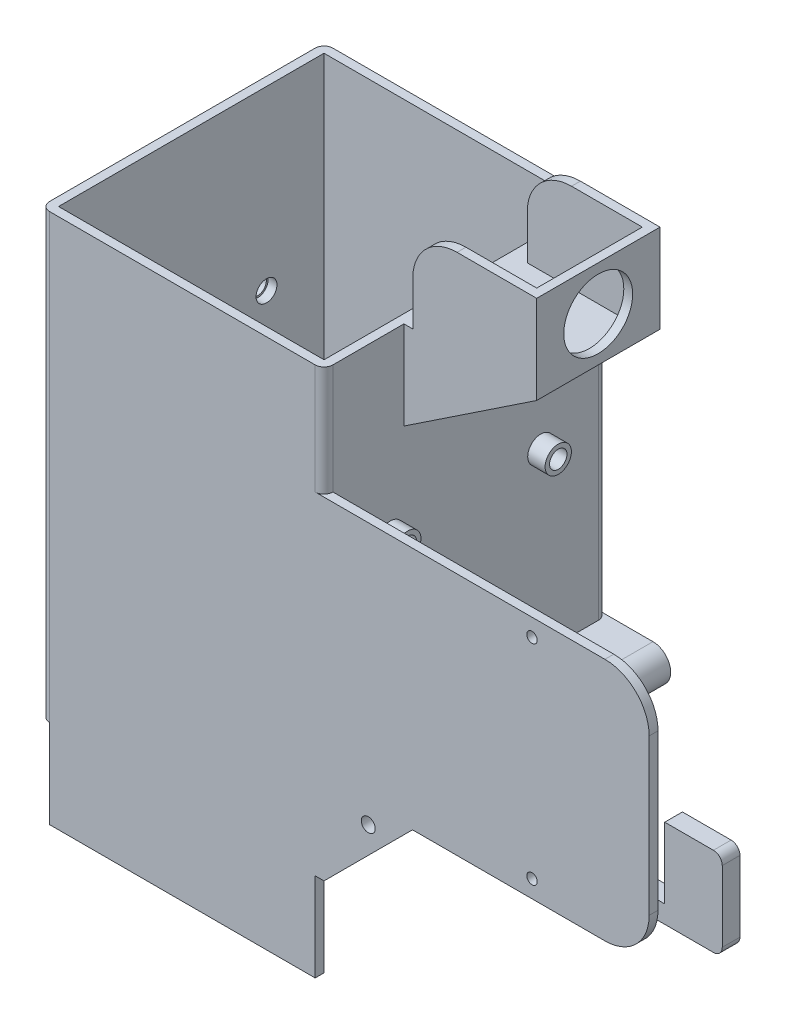
SolidWorks part; units mm, degrees
ref_plane "Front Plane" through (0, 0, 0) normal (0, 0, 1) x (1, 0, 0)
ref_plane "Top Plane" through (0, 0, 0) normal (0, 1, 0) x (1, 0, 0)
ref_plane "Right Plane" through (0, 0, 0) normal (1, 0, 0) x (0, 0, -1)
sketch "Sketch1" plane through (0, 0, 0) normal (0, 1, 0) x (1, 0, 0)
  line L1 (0, 0) -> (81.28, 0)
  line L2 (0, 0) -> (0, 81.28)
  line L3 (0, 81.28) -> (81.28, 81.28)
  line L4 (81.28, 0) -> (81.28, 81.28)
  line L5 (2.54, 2.54) -> (78.74, 2.54)
  line L6 (2.54, 2.54) -> (2.54, 78.74)
  line L7 (2.54, 78.74) -> (78.74, 78.74)
  line L8 (78.74, 2.54) -> (78.74, 78.74)
  dimension "D1" = 2.54
  dimension "D2" = 2.54
  dimension "D3" = 2.54
  dimension "D4" = 2.54
  dimension "D5" = 76.2
  dimension "D6" = 76.2
extrude "Boss-Extrude1" add sketch "Sketch1" along normal blind 177.8
sketch "Sketch2" plane through (0, 0, 0) normal (1, 0, 0) x (0, 0, -1)
  line L0 (109.0297, 38.1) -> (-23.7268, 38.1) construction
  line L1 (81.28, 0) -> (0, 0) construction
  line L2 (40.64, -8.2418) -> (40.64, 63.9342) construction
  line L3 (81.28, 177.8) -> (81.28, 0) construction
  line L5 (66.04, 0) -> (63.5, 0)
  line L6 (66.04, 0) -> (66.04, 38.1)
  line L7 (66.04, 38.1) -> (63.5, 38.1)
  line L8 (63.5, 0) -> (63.5, 38.1)
  dimension "D1" = 38.1
  dimension "D2" = 40.64
  dimension "D3" = 2.54
  dimension "D4" = 15.24
extrude "Boss-Extrude2" add sketch "Sketch2" against normal blind 25.4
sketch "Sketch3" plane through (0, 0, 0) normal (0, 0, 1) x (1, 0, 0)
  line L1 (81.28, 0) -> (78.74, 0)
  line L2 (81.28, 0) -> (81.28, 25.4)
  line L3 (81.28, 25.4) -> (78.74, 25.4)
  line L4 (78.74, 0) -> (78.74, 25.4)
  dimension "D1" = 2.54
  dimension "D2" = 25.4
extrude "Cut-Extrude1" cut sketch "Sketch3" against normal through all
sketch "Sketch7" plane through (0, 0, 0) normal (0, 0, 1) x (1, 0, 0)
  line L0 (81.28, 25.4) -> (106.68, 50.8)
  line L1 (106.68, 50.8) -> (81.28, 50.8)
  line L2 (81.28, 177.8) -> (81.28, 25.4) construction
  line L3 (81.28, 50.8) -> (81.28, 25.4)
  dimension "D1" = 45
  dimension "D2" = 25.4
extrude "Boss-Extrude3" add sketch "Sketch7" against normal blind 12.7
sketch "Sketch10" plane through (0, 0, -81.28) normal (0, 0, -1) x (-1, 0, 0)
  line L0 (-81.28, 25.4) -> (-81.28, 50.8)
  line L1 (-81.28, 177.8) -> (-81.28, 25.4) construction
  line L2 (-81.28, 50.8) -> (-106.68, 50.8)
  line L3 (-106.68, 50.8) -> (-81.28, 25.4)
  dimension "D1" = 45
  dimension "D2" = 25.4
extrude "Boss-Extrude4" add sketch "Sketch10" against normal blind 12.7
sketch "Sketch14" plane through (81.28, 0, 0) normal (1, 0, 0) x (0, 0, -1)
  line L0 (38.1, 50.8) -> (38.1, 25.4)
  line L1 (68.58, 25.4) -> (12.7, 25.4) construction
  line L2 (38.1, 25.4) -> (43.18, 25.4)
  line L3 (43.18, 25.4) -> (43.18, 50.8)
  line L4 (43.18, 50.8) -> (38.1, 50.8)
  line L5 (68.58, 50.8) -> (68.58, 25.4) construction
  dimension "D1" = 5.08
  dimension "D2" = 25.4
  dimension "D3" = 25.4
extrude "Boss-Extrude6" add sketch "Sketch14" along normal blind 76.2
sketch "Sketch16" plane through (0, 0, -38.1) normal (0, 0, 1) x (1, 0, 0)
  line L0 (157.48, 50.8) -> (81.28, 50.8) construction
  line L1 (140.97, 50.8) -> (117.84, 50.8)
  line L2 (140.97, 50.8) -> (140.97, 30.48)
  line L3 (140.97, 30.48) -> (117.84, 30.48)
  line L4 (117.84, 50.8) -> (117.84, 30.48)
  line L5 (157.48, 50.8) -> (157.48, 25.4) construction
  line L6 (157.48, 25.4) -> (81.28, 25.4) construction
  dimension "D1" = 16.51
  dimension "D2" = 23.13
  dimension "D3" = 5.08
extrude "Cut-Extrude2" cut sketch "Sketch16" against normal up to next
sketch "Sketch22" plane through (0, 0, 0) normal (0, 0, 1) x (1, 0, 0)
  line L0 (93.98, 45.72) -> (101.6, 45.72) construction
  line L1 (106.68, 50.8) -> (81.28, 50.8) construction
  line L2 (93.98, 50.8) -> (93.98, 45.72) construction
  line L4 (81.28, 25.4) -> (106.68, 50.8) construction
  circle A0 centre (93.98, 45.72) radius 2
  dimension "D3" = 4
  dimension "D1" = 5.08
  dimension "D2" = 12.7
extrude "Cut-Extrude6" cut sketch "Sketch22" against normal through all
sketch "Sketch28" plane through (81.28, 0, 0) normal (1, 0, 0) x (0, 0, -1)
  line L0 (40.64, 175.678) -> (40.64, 120.0937) construction
  line L1 (40.64, 184.0271) -> (40.64, -14.0592) construction
  line L2 (0, 177.8) -> (81.28, 177.8) construction
  line L3 (0, 177.8) -> (0, 50.8) construction
  line L5 (58.34, 177.8) -> (22.94, 177.8)
  line L6 (58.34, 177.8) -> (58.34, 127)
  line L7 (58.34, 127) -> (22.94, 127)
  line L8 (22.94, 177.8) -> (22.94, 127)
  line L9 (58.34, 177.8) -> (22.94, 127) construction
  line L10 (58.34, 127) -> (22.94, 177.8) construction
  point P8 (40.64, 109.22)
  dimension "D2" = 40.64
  dimension "D3" = 50.8
  dimension "D4" = 35.4
extrude "Boss-Extrude7" add sketch "Sketch28" along normal blind 38.1
sketch "Sketch30" plane through (0, 0, -22.94) normal (0, 0, 1) x (1, 0, 0)
  line L0 (81.28, 127) -> (119.38, 127)
  line L1 (119.38, 127) -> (119.38, 152.4)
  line L3 (119.38, 152.4) -> (81.28, 127)
  dimension "D1" = 25.4
  dimension "D2" = 33.69
extrude "Cut-Extrude8" cut sketch "Sketch30" against normal up to next
sketch "Sketch32" plane through (0, 177.8, 0) normal (0, 1, 0) x (1, 0, 0)
  line L0 (119.38, 58.34) -> (81.28, 58.34) construction
  line L1 (83.82, 55.8) -> (116.84, 55.8)
  line L2 (83.82, 55.8) -> (83.82, 25.48)
  line L3 (83.82, 25.48) -> (116.84, 25.48)
  line L4 (116.84, 55.8) -> (116.84, 25.48)
  line L5 (83.82, 55.8) -> (116.84, 25.48) construction
  line L6 (83.82, 25.48) -> (116.84, 55.8) construction
  line L7 (119.38, 58.34) -> (119.38, 22.94) construction
  line L8 (119.38, 22.94) -> (81.28, 22.94) construction
  line L9 (81.28, 58.34) -> (81.28, 81.28) construction
  point P0 (100.33, 40.64)
  dimension "D1" = 2.54
  dimension "D2" = 2.54
  dimension "D3" = 2.54
  dimension "D4" = 2.54
extrude "Cut-Extrude9" cut sketch "Sketch32" against normal blind 25.4
sketch "Sketch34" plane through (119.38, 0, 0) normal (1, 0, 0) x (0, 0, -1)
  line L0 (40.593, 147.7754) -> (40.593, 78.4323) construction
  line L1 (11.6001, 165.1) -> (93.4551, 165.1) construction
  line L2 (22.94, 177.8) -> (22.94, 152.4) construction
  line L3 (58.34, 177.8) -> (22.94, 177.8) construction
  circle A0 centre (40.593, 165.1) radius 9.89
  dimension "D3" = 19.78
  dimension "D1" = 17.653
  dimension "D2" = 12.7
extrude "Cut-Extrude13" cut sketch "Sketch34" against normal up to surface (40.64 mm away) up to face at (78.74, 101.6, -40.64)
sketch "Sketch37" plane through (0, 0, -63.5) normal (0, 0, 1) x (1, 0, 0)
  line L0 (-25.4, 38.1) -> (0, 38.1)
  line L1 (0, 38.1) -> (0, 52.7647)
  line L2 (0, 52.7647) -> (-25.4, 38.1)
  dimension "D1" = 30
extrude "Boss-Extrude9" add sketch "Sketch37" against normal up to surface (2.54 mm away) up to face at (-12.7, 19.05, -66.04)
sketch "Sketch38" plane through (0, 0, 0) normal (0, 0, 1) x (1, 0, 0)
  line L1 (0, 0) -> (2.54, 0)
  line L2 (0, 0) -> (0, 25.4)
  line L3 (0, 25.4) -> (2.54, 25.4)
  line L4 (2.54, 0) -> (2.54, 25.4)
  dimension "D1" = 25.4
  dimension "D2" = 2.54
extrude "Cut-Extrude15" cut sketch "Sketch38" against normal up to surface (63.5 mm away) up to face at (-12.7, 22.7162, -63.5)
sketch "Sketch40" plane through (81.28, 0, 0) normal (1, 0, 0) x (0, 0, -1)
  line L0 (-23.3344, 101.6) -> (103.8421, 101.6) construction
  line L1 (38.1, 25.4) -> (12.7, 25.4) construction
  line L2 (19.05, 177.8) -> (19.05, 25.4) construction
  line L3 (62.23, 177.8) -> (62.23, 25.4) construction
  line L6 (0, 177.8) -> (0, 50.8) construction
  line L7 (81.28, 177.8) -> (81.28, 50.8) construction
  line L8 (0, 177.8) -> (22.94, 177.8) construction
  line L9 (58.34, 177.8) -> (81.28, 177.8) construction
  line L10 (68.58, 25.4) -> (43.18, 25.4) construction
  circle A0 centre (19.05, 101.6) radius 3
  circle A1 centre (62.23, 101.6) radius 3
  dimension "D4" = 6
  dimension "D5" = 6
  dimension "D1" = 76.2
  dimension "D2" = 19.05
  dimension "D3" = 19.05
extrude "Cut-Extrude17" cut sketch "Sketch40" against normal up to surface (81.28 mm away) up to face at (0, 63.9912, -52.705)
sketch "Sketch41" plane through (81.28, 0, 0) normal (1, 0, 0) x (0, 0, -1)
  circle A0 centre (19.05, 101.6) radius 3.77
  circle A1 centre (19.05, 101.6) radius 2.5
  circle A2 centre (62.23, 101.6) radius 3.77
  circle A4 centre (62.23, 101.6) radius 2.5
  dimension "D1" = 1.27
  dimension "D2" = 1.27
extrude "Boss-Extrude10" add sketch "Sketch41" along normal blind 5
sketch "Sketch42" plane through (0, 0, 0) normal (-1, 0, 0) x (0, 0, 1)
  circle A0 centre (-62.23, 101.6) radius 2.5
  circle A1 centre (-62.23, 101.6) radius 3.77
  circle A2 centre (-19.05, 101.6) radius 2.5
  circle A3 centre (-19.05, 101.6) radius 3.77
  dimension "D1" = 1.27
  dimension "D2" = 1.27
extrude "Boss-Extrude11" add sketch "Sketch42" along normal blind 5
sketch "Sketch43" plane through (0, 177.8, 0) normal (0, 1, 0) x (1, 0, 0)
  line L1 (83.82, 58.34) -> (83.82, 22.94)
  line L3 (78.74, 2.54) -> (2.54, 2.54)
  line L4 (2.54, 2.54) -> (78.74, 2.54) construction
  line L5 (2.54, 2.54) -> (2.54, 78.74)
  line L6 (2.54, 78.74) -> (78.74, 78.74)
  line L11 (81.28, 81.28) -> (0, 81.28)
  line L12 (0, 81.28) -> (0, 0)
  line L13 (0, 0) -> (81.28, 0)
  line L19 (81.28, 81.28) -> (81.28, 58.34)
  line L21 (81.28, 58.34) -> (83.82, 58.34)
  line L22 (81.28, 0) -> (81.28, 22.94)
  line L23 (81.28, 22.94) -> (83.82, 22.94)
  line L24 (78.74, 78.74) -> (78.74, 2.54)
  line L25 (83.82, 55.8) -> (83.82, 25.48) construction
  line L26 (119.38, 22.94) -> (81.28, 22.94) construction
  line L27 (81.28, 81.28) -> (0, 81.28) construction
extrude "Cut-Extrude20" cut sketch "Sketch43" against normal blind 25.4
sketch "Sketch44" plane through (0, 0, 0) normal (0, 0, 1) x (1, 0, 0)
  line L0 (0, 152.4) -> (0, 25.4) construction
  line L1 (0, 50.8) -> (174.6, 50.8)
  line L2 (0, 50.8) -> (0, 120.8)
  line L3 (0, 120.8) -> (174.6, 120.8)
  line L4 (174.6, 50.8) -> (174.6, 120.8)
  line L5 (106.68, 50.8) -> (81.28, 50.8) construction
  line L6 (-25.4, 38.1) -> (-25.4, 0) construction
  line L7 (140.97, 50.8) -> (140.97, 120.8) construction
  line L8 (140.97, 30.48) -> (140.97, 50.8) construction
  circle A0 centre (140.97, 115.8) radius 1.5
  circle A1 centre (140.97, 55.8) radius 1.5
  dimension "D3" = 3
  dimension "D1" = 200
  dimension "D2" = 70
  dimension "D4" = 60
  dimension "D5" = 5
extrude "Boss-Extrude12" add sketch "Sketch44" against normal blind 2.54
fillet "Fillet1" radius 5.08 2 edges at (106.68, 50.8, -7.62) (106.68, 50.8, -74.93)
fillet "Fillet2" radius 12.7 2 edges at (174.6, 120.8, -1.27) (174.6, 50.8, -1.27)
fillet "Fillet3" radius 2.54 2 edges at (157.48, 50.8, -40.64) (157.48, 25.4, -40.64)
fillet "Fillet7" radius 12.7 1 edges at (-25.4, 38.1, -64.77)
fillet "Fillet9" radius 12.7 2 edges at (83.82, 177.8, -24.21) (83.82, 177.8, -57.07)
sketch "Sketch53" plane through (0, 0, 0) normal (0, -1, 0) x (-1, 0, 0)
  line L0 (-35.6591, 81.28) -> (-35.6591, 78.74)
  line L1 (-78.74, 81.28) -> (0, 81.28) construction
  line L2 (-78.74, 78.74) -> (-2.54, 78.74) construction
  line L3 (-35.6591, 78.74) -> (-45.72, 78.74)
  line L4 (-45.72, 78.74) -> (-45.72, 111.76)
  line L5 (-45.72, 111.76) -> (-15.24, 111.76)
  line L6 (-15.24, 111.76) -> (-15.24, 106.68)
  line L7 (-15.24, 106.68) -> (-40.64, 106.68)
  line L8 (-40.64, 106.68) -> (-40.64, 81.28)
  line L9 (-40.64, 81.28) -> (-35.6591, 81.28)
  line L12 (-81.28, 81.28) -> (-81.28, 96.103) construction
  line L13 (0, 81.28) -> (0, 96.103) construction
  dimension "D1" = 25.4
  dimension "D2" = 5.08
  dimension "D3" = 5.08
  dimension "D4" = 25.4
  dimension "D5" = 40.64
extrude "Boss-Extrude20" add sketch "Sketch53" against normal blind 88.9
sketch "Sketch54" plane through (0, 0, -111.76) normal (0, 0, -1) x (-1, 0, 0)
  line L0 (-30.48, 0) -> (-30.48, 88.9) construction
  line L1 (-15.24, 0) -> (-45.72, 0) construction
  line L2 (-15.24, 88.9) -> (-45.72, 88.9) construction
  circle A0 centre (-30.48, 76.2) radius 2.5
  circle A1 centre (-30.48, 44.45) radius 2.5
  circle A2 centre (-30.48, 12.7) radius 2.5
  dimension "D1" = 5
  dimension "D2" = 5
  dimension "D3" = 5
  dimension "D4" = 12.7
  dimension "D5" = 12.7
  dimension "D6" = 44.45
extrude "Cut-Extrude21" cut sketch "Sketch54" against normal up to next
fillet "Fillet11" radius 2.54 4 edges at (15.24, 44.45, -111.76) (15.24, 88.9, -109.22) (15.24, 44.45, -106.68) (15.24, 0, -109.22)
fillet "Fillet12" radius 2.54 4 edges at (81.28, 136.6, 0) (81.28, 101.6, -81.28) (0, 76.2, -81.28) (0, 88.9, 0)
